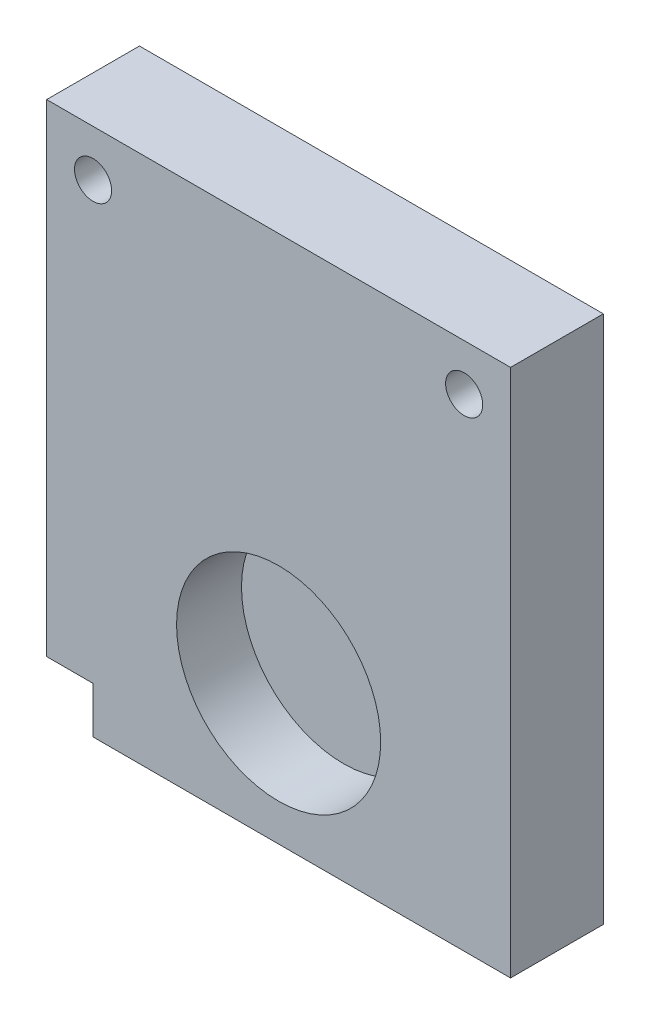
SolidWorks part; units mm, degrees
material "PVC rigide"
ref_plane "Plan de face" through (0, 0, 0) normal (0, 0, 1) x (1, 0, 0)
ref_plane "Plan de dessus" through (0, 0, 0) normal (0, 1, 0) x (1, 0, 0)
ref_plane "Plan de droite" through (0, 0, 0) normal (1, 0, 0) x (0, 0, -1)
sketch "Esquisse1" plane through (0, 0, 0) normal (0, 0, 1) x (1, 0, 0)
  line L0 (-20.372, -12.2825) -> (-15.372, -12.2825)
  line L1 (-20.372, 39.7175) -> (29.628, 39.7175)
  line L2 (-20.372, 39.7175) -> (-20.372, -12.2825)
  line L3 (-15.372, -17.2825) -> (29.628, -17.2825)
  line L4 (29.628, 39.7175) -> (29.628, -17.2825)
  line L5 (-15.372, -12.2825) -> (-15.372, -17.2825)
  dimension "D4" = 5
  dimension "D1" = 50
  dimension "D2" = 57
  dimension "D3" = 5
extrude "Boss.-Extru.1" add sketch "Esquisse1" along normal blind 10
sketch "Esquisse2" plane through (0, -17.2825, 0) normal (0, -1, 0) x (1, 0, 0)
  line L0 (-20.372, 5) -> (29.628, 5) construction
  line L1 (-20.372, 10) -> (-20.372, 0) construction
  line L2 (29.628, 10) -> (29.628, 0) construction
  circle A0 centre (-10.372, 5) radius 2
  circle A1 centre (19.628, 5) radius 2
  dimension "D1" = 4
  dimension "D2" = 10
  dimension "D3" = 10
extrude "Enlèv. mat.-Extru.1" cut sketch "Esquisse2" against normal blind 10
sketch "Esquisse3" plane through (0, 0, 10) normal (0, 0, 1) x (1, 0, 0)
  line L0 (-25.973, 34.7175) -> (39.229, 34.7175) construction
  line L1 (29.628, 39.7175) -> (-20.372, 39.7175) construction
  line L2 (-20.372, 39.7175) -> (-20.372, -12.2825) construction
  line L3 (29.628, -17.2825) -> (29.628, 39.7175) construction
  circle A0 centre (-15.372, 34.7175) radius 2
  circle A1 centre (24.628, 34.7175) radius 2
  dimension "D2" = 4
  dimension "D1" = 5
  dimension "D3" = 5
  dimension "D4" = 5
extrude "Enlèv. mat.-Extru.2" cut sketch "Esquisse3" against normal through all
chamfer "Chanfrein1" distance 2.5 angle 45 2 edges at (26.628, 34.7175, 0) (-13.372, 34.7175, 0)
sketch "Esquisse4" plane through (0, 0, 10) normal (0, 0, 1) x (1, 0, 0)
  line L0 (-32.372, -2.2825) -> (112.9613, -2.2825) construction
  line L1 (4.628, -17.2825) -> (4.628, 39.7175) construction
  line L3 (-15.372, -17.2825) -> (29.628, -17.2825) construction
  line L4 (29.628, 39.7175) -> (-20.372, 39.7175) construction
  circle A0 centre (4.628, -2.2825) radius 11
  point P17 (4.628, -2.2825)
  dimension "D1" = 22
  dimension "D2" = 15
extrude "Enlèv. mat.-Extru.3" cut sketch "Esquisse4" against normal blind 7
